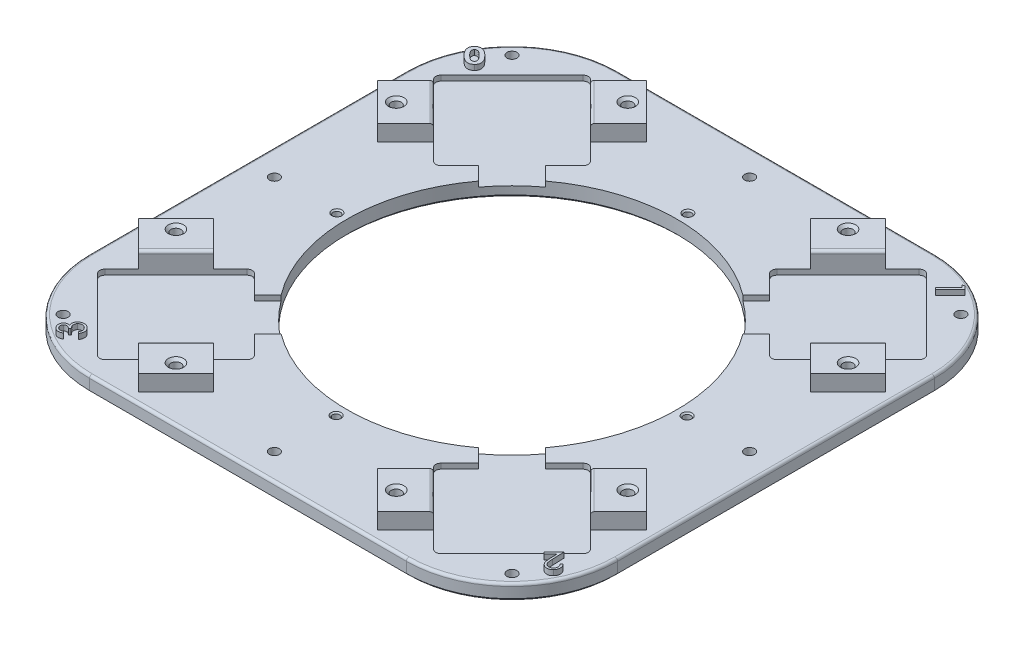
SolidWorks part; units mm, degrees
ref_plane "Спереди" through (0, 0, 0) normal (0, 0, 1) x (1, 0, 0)
ref_plane "Сверху" through (0, 0, 0) normal (0, 1, 0) x (1, 0, 0)
ref_plane "Справа" through (0, 0, 0) normal (1, 0, 0) x (0, 0, -1)
sketch "Эскиз1" plane through (0, 0, 0) normal (0, 1, 0) x (1, 0, 0)
  line L1 (-100, -100) -> (100, -100)
  line L2 (-100, -100) -> (-100, 100)
  line L3 (-100, 100) -> (100, 100)
  line L4 (100, -100) -> (100, 100)
  line L5 (0, 100) -> (0, -100) construction
  line L6 (-100, 0) -> (100, 0) construction
  line L11 (0, 75) -> (0, -75) construction
  line L12 (-39.5, 0) -> (39.5, 0) construction
  line L13 (-85, -85) -> (85, -85) construction
  line L14 (-85, -85) -> (-85, 85) construction
  line L15 (-85, 85) -> (85, 85) construction
  line L16 (85, -85) -> (85, 85) construction
  line L17 (0, 85) -> (0, -85) construction
  line L18 (-85, 0) -> (85, 0) construction
  circle A8 centre (-90, 0) radius 1.9
  circle A9 centre (0, 90) radius 1.9
  circle A10 centre (90, 0) radius 1.9
  circle A11 centre (0, -90) radius 1.9
  circle A12 centre (-85, 85) radius 1.9
  circle A13 centre (85, 85) radius 1.9
  circle A14 centre (85, -85) radius 1.9
  circle A15 centre (-85, -85) radius 1.9
  point P0 (0, 0)
  point P4 (0, 0)
  point P11 (0, 0)
  point P27 (0, 0)
  dimension "D6" = 90
  dimension "D2" = 3.8
  dimension "D1" = 200
  dimension "D8" = 170
  dimension "D7" = 4
extrude "Бобышка-Вытянуть1" add sketch "Эскиз1" along normal blind 6
sketch "Эскиз2" plane through (0, 6, 0) normal (0, 1, 0) x (1, 0, 0)
  line L0 (0, 72.2532) -> (0, 0) construction
  line L1 (0, 0) -> (100, 100) construction
  line L2 (63.6396, 33.9411) -> (33.9411, 63.6396)
  line L3 (63.6396, 33.9411) -> (93.3381, 63.6396)
  line L4 (33.9411, 63.6396) -> (63.6396, 93.3381)
  line L5 (93.3381, 63.6396) -> (63.6396, 93.3381)
  line L6 (63.6396, 33.9411) -> (63.6396, 93.3381) construction
  line L7 (33.9411, 63.6396) -> (93.3381, 63.6396) construction
  line L8 (33.9411, -63.6396) -> (63.6396, -33.9411)
  line L9 (33.9411, -63.6396) -> (63.6396, -93.3381)
  line L10 (63.6396, -93.3381) -> (93.3381, -63.6396)
  line L11 (63.6396, -33.9411) -> (93.3381, -63.6396)
  line L12 (-63.6396, -33.9411) -> (-33.9411, -63.6396)
  line L13 (-63.6396, -33.9411) -> (-93.3381, -63.6396)
  line L14 (-93.3381, -63.6396) -> (-63.6396, -93.3381)
  line L15 (-33.9411, -63.6396) -> (-63.6396, -93.3381)
  line L16 (-33.9411, 63.6396) -> (-63.6396, 33.9411)
  line L17 (-33.9411, 63.6396) -> (-63.6396, 93.3381)
  line L18 (-63.6396, 93.3381) -> (-93.3381, 63.6396)
  line L19 (-63.6396, 33.9411) -> (-93.3381, 63.6396)
  line L20 (0, 0) -> (119.0497, 0) construction
  point P6 (63.6396, 63.6396)
  point P24 (0, 0)
  dimension "D1" = 42
  dimension "D2" = 90
  dimension "D4" = 63.6396
  dimension "D5" = 63.6396
  dimension "D3" = 4
extrude "Вырез-Вытянуть1" cut sketch "Эскиз2" against normal blind 2
fillet "Скругление1" radius 2 16 edges at (63.6396, 5, -33.9411) (33.9411, 5, -63.6396) (93.3381, 5, -63.6396) (63.6396, 5, -93.3381) (-63.6396, 5, -93.3381) (-63.6396, 5, -33.9411) (-93.3381, 5, -63.6396) (-33.9411, 5, -63.6396) (63.6396, 5, 93.3381) (93.3381, 5, 63.6396) (63.6396, 5, 33.9411) (33.9411, 5, 63.6396) (-63.6396, 5, 93.3381) (-33.9411, 5, 63.6396) (-63.6396, 5, 33.9411) (-93.3381, 5, 63.6396)
sketch "Эскиз3" plane through (0, 6, 0) normal (0, 1, 0) x (1, 0, 0)
  line L0 (48.7904, 48.7904) -> (67.3817, 67.3817) construction
  line L1 (35.3553, 62.2254) -> (62.2254, 35.3553) construction
  line L2 (48.7904, 78.4889) -> (78.4889, 48.7904) construction
  line L3 (62.2254, 91.9239) -> (35.3553, 65.0538) construction
  line L4 (65.0538, 35.3553) -> (91.9239, 62.2254) construction
  line L5 (41.7193, 71.4178) -> (55.8614, 85.5599)
  line L6 (41.7193, 71.4178) -> (31.1127, 82.0244)
  line L7 (55.8614, 85.5599) -> (45.2548, 96.1665)
  line L8 (31.1127, 82.0244) -> (45.2548, 96.1665)
  line L9 (62.2254, 91.9239) -> (35.3553, 65.0538) construction
  line L10 (85.5599, 55.8614) -> (96.1665, 45.2548)
  line L11 (82.0244, 31.1127) -> (96.1665, 45.2548)
  line L12 (71.4178, 41.7193) -> (82.0244, 31.1127)
  line L13 (71.4178, 41.7193) -> (85.5599, 55.8614)
  line L44 (65.0538, 35.3553) -> (91.9239, 62.2254) construction
  line L45 (0, 128.3294) -> (0, 0) construction
  line L64 (0, 0) -> (145.1139, 0) construction
  line L65 (62.2254, 91.9239) -> (35.3553, 65.0538) construction
  line L90 (48.7904, -78.4889) -> (78.4889, -48.7904) construction
  line L91 (48.7904, -48.7904) -> (67.3817, -67.3817) construction
  line L92 (71.4178, -41.7193) -> (85.5599, -55.8614)
  line L93 (71.4178, -41.7193) -> (82.0244, -31.1127)
  line L94 (82.0244, -31.1127) -> (96.1665, -45.2548)
  line L95 (85.5599, -55.8614) -> (96.1665, -45.2548)
  line L96 (31.1127, -82.0244) -> (45.2548, -96.1665)
  line L97 (55.8614, -85.5599) -> (45.2548, -96.1665)
  line L98 (41.7193, -71.4178) -> (31.1127, -82.0244)
  line L99 (41.7193, -71.4178) -> (55.8614, -85.5599)
  line L100 (-48.7904, -48.7904) -> (-67.3817, -67.3817) construction
  line L101 (-48.7904, -78.4889) -> (-78.4889, -48.7904) construction
  line L102 (-48.7904, 78.4889) -> (-78.4889, 48.7904) construction
  line L103 (-48.7904, 48.7904) -> (-67.3817, 67.3817) construction
  line L104 (-41.7193, -71.4178) -> (-55.8614, -85.5599)
  line L105 (-41.7193, -71.4178) -> (-31.1127, -82.0244)
  line L106 (-55.8614, -85.5599) -> (-45.2548, -96.1665)
  line L107 (-31.1127, -82.0244) -> (-45.2548, -96.1665)
  line L108 (-85.5599, -55.8614) -> (-96.1665, -45.2548)
  line L109 (-82.0244, -31.1127) -> (-96.1665, -45.2548)
  line L110 (-71.4178, -41.7193) -> (-82.0244, -31.1127)
  line L111 (-71.4178, -41.7193) -> (-85.5599, -55.8614)
  line L112 (-71.4178, 41.7193) -> (-85.5599, 55.8614)
  line L113 (-71.4178, 41.7193) -> (-82.0244, 31.1127)
  line L114 (-82.0244, 31.1127) -> (-96.1665, 45.2548)
  line L115 (-85.5599, 55.8614) -> (-96.1665, 45.2548)
  line L116 (-31.1127, 82.0244) -> (-45.2548, 96.1665)
  line L117 (-55.8614, 85.5599) -> (-45.2548, 96.1665)
  line L118 (-41.7193, 71.4178) -> (-31.1127, 82.0244)
  line L119 (-41.7193, 71.4178) -> (-55.8614, 85.5599)
  point P16 (48.7904, 78.4889)
  dimension "D1" = 20
  dimension "D2" = 15
extrude "Бобышка-Вытянуть3" add sketch "Эскиз3" along normal blind 6
fillet "Скругление4" radius 40 4 edges at (100, 3, -100) (100, 3, 100) (-100, 3, 100) (-100, 3, -100)
sketch "Эскиз4" plane through (0, 12, 0) normal (0, 1, 0) x (1, 0, 0)
  line L0 (89.0955, 38.1838) -> (38.1838, 89.0955) construction
  line L1 (82.0244, 31.1127) -> (96.1665, 45.2548) construction
  line L2 (45.2548, 96.1665) -> (31.1127, 82.0244) construction
  line L3 (41.7193, 71.4178) -> (55.8614, 85.5599) construction
  line L4 (48.7904, 48.7904) -> (78.4889, 78.4889) construction
  line L5 (35.3553, 62.2254) -> (62.2254, 35.3553) construction
  line L6 (91.9239, 65.0538) -> (65.0538, 91.9239) construction
  line L7 (0, 119.2498) -> (0, 0) construction
  line L8 (0, 0) -> (156.895, 0) construction
  line L9 (48.7904, -48.7904) -> (78.4889, -78.4889) construction
  line L10 (89.0955, -38.1838) -> (38.1838, -89.0955) construction
  line L11 (-89.0955, -38.1838) -> (-38.1838, -89.0955) construction
  line L12 (-48.7904, -48.7904) -> (-78.4889, -78.4889) construction
  line L13 (-48.7904, 48.7904) -> (-78.4889, 78.4889) construction
  line L14 (-89.0955, 38.1838) -> (-38.1838, 89.0955) construction
  circle A0 centre (41.7193, 85.5599) radius 1.9
  circle A1 centre (85.5599, 41.7193) radius 1.9
  circle A14 centre (85.5599, -41.7193) radius 1.9
  circle A15 centre (41.7193, -85.5599) radius 1.9
  circle A16 centre (-41.7193, -85.5599) radius 1.9
  circle A17 centre (-85.5599, -41.7193) radius 1.9
  circle A18 centre (-85.5599, 41.7193) radius 1.9
  circle A19 centre (-41.7193, 85.5599) radius 1.9
  dimension "D1" = 10
  dimension "D3" = 62
  dimension "D2" = 3.8
  dimension "D4" = 31
extrude "Вырез-Вытянуть2" cut sketch "Эскиз4" against normal blind 8
sketch "Эскиз7" plane through (0, 6, 0) normal (0, 1, 0) x (1, 0, 0)
  line L0 (0, 76.3028) -> (0, 0) construction
  line L1 (0, 0) -> (74.3797, 74.3797) construction
  line L2 (20, 6) -> (60, 6)
  line L3 (-6, 20) -> (6, 20)
  line L4 (-6, 20) -> (-6, 60)
  line L5 (-6, 60) -> (6, 60)
  line L6 (6, 20) -> (6, 60)
  line L7 (0, 60) -> (0, 20) construction
  line L8 (-6, 40) -> (6, 40) construction
  line L9 (20, 6) -> (20, -6)
  line L10 (20, -6) -> (60, -6)
  line L11 (60, 6) -> (60, -6)
  line L12 (6, -20) -> (6, -60)
  line L13 (6, -20) -> (-6, -20)
  line L14 (-6, -20) -> (-6, -60)
  line L15 (6, -60) -> (-6, -60)
  line L16 (-20, -6) -> (-60, -6)
  line L17 (-20, -6) -> (-20, 6)
  line L18 (-20, 6) -> (-60, 6)
  line L19 (-60, -6) -> (-60, 6)
  circle A0 centre (28.2843, 28.2843) radius 12
  circle A1 centre (28.2843, -28.2843) radius 12
  circle A2 centre (-28.2843, -28.2843) radius 12
  circle A3 centre (-28.2843, 28.2843) radius 12
  point P6 (0, 40)
  point P15 (0, 0)
  point P32 (0, 0)
  dimension "D1" = 40
  dimension "D2" = 24
  dimension "D4" = 12
  dimension "D5" = 40
  dimension "D6" = 40
  dimension "D3" = 4
  dimension "D7" = 4
extrude "Вырез-Вытянуть3" cut sketch "Эскиз7" against normal blind 6
sketch "Эскиз8" plane through (0, 6, 0) normal (0, 1, 0) x (1, 0, 0)
  line L0 (48.7904, 48.7904) -> (72.3205, 72.3205) construction
  line L1 (35.3553, 62.2254) -> (62.2254, 35.3553) construction
  line L2 (44.5477, 31.8198) -> (31.8198, 44.5477)
  line L3 (44.5477, 31.8198) -> (65.7609, 53.033)
  line L4 (31.8198, 44.5477) -> (53.033, 65.7609)
  line L5 (65.7609, 53.033) -> (53.033, 65.7609)
  line L6 (44.5477, 31.8198) -> (53.033, 65.7609) construction
  line L7 (31.8198, 44.5477) -> (65.7609, 53.033) construction
  line L20 (0, 107.5006) -> (0, 0) construction
  line L21 (0, 0) -> (140.6034, 0) construction
  line L22 (31.8198, -44.5477) -> (65.7609, -53.033) construction
  line L23 (44.5477, -31.8198) -> (53.033, -65.7609) construction
  line L24 (48.7904, -48.7904) -> (72.3205, -72.3205) construction
  line L25 (65.7609, -53.033) -> (53.033, -65.7609)
  line L26 (31.8198, -44.5477) -> (53.033, -65.7609)
  line L27 (44.5477, -31.8198) -> (65.7609, -53.033)
  line L28 (44.5477, -31.8198) -> (31.8198, -44.5477)
  line L29 (-48.7904, -48.7904) -> (-72.3205, -72.3205) construction
  line L30 (-44.5477, -31.8198) -> (-53.033, -65.7609) construction
  line L31 (-31.8198, -44.5477) -> (-65.7609, -53.033) construction
  line L32 (-31.8198, 44.5477) -> (-65.7609, 53.033) construction
  line L33 (-44.5477, 31.8198) -> (-53.033, 65.7609) construction
  line L34 (-48.7904, 48.7904) -> (-72.3205, 72.3205) construction
  line L35 (-44.5477, -31.8198) -> (-31.8198, -44.5477)
  line L36 (-44.5477, -31.8198) -> (-65.7609, -53.033)
  line L37 (-31.8198, -44.5477) -> (-53.033, -65.7609)
  line L38 (-65.7609, -53.033) -> (-53.033, -65.7609)
  line L39 (-65.7609, 53.033) -> (-53.033, 65.7609)
  line L40 (-31.8198, 44.5477) -> (-53.033, 65.7609)
  line L41 (-44.5477, 31.8198) -> (-65.7609, 53.033)
  line L42 (-44.5477, 31.8198) -> (-31.8198, 44.5477)
  point P24 (0, 16.9706)
  dimension "D1" = 18
  dimension "D2" = 30
extrude "Вырез-Вытянуть4" cut sketch "Эскиз8" against normal blind 2
fillet "Скругление6" radius 1 8 edges at (78.4889, 12, -48.7904) (48.7904, 12, -78.4889) (-78.4889, 12, 48.7904) (-48.7904, 12, 78.4889) (48.7904, 12, 78.4889) (78.4889, 12, 48.7904) (-78.4889, 12, -48.7904) (-48.7904, 12, -78.4889)
sketch "Эскиз9" plane through (0, 6, 0) normal (0, 1, 0) x (1, 0, 0)
  line L0 (-70.7105, 0.151) -> (0.151, 70.7105) construction
  line L1 (-70.7105, 0.151) -> (-0.151, -70.7105) construction
  line L2 (0.151, 70.7105) -> (70.7105, -0.151) construction
  line L3 (-0.151, -70.7105) -> (70.7105, -0.151) construction
  line L4 (-70.7105, 0.151) -> (70.7105, -0.151) construction
  line L5 (0.151, 70.7105) -> (-0.151, -70.7105) construction
  line L6 (0, 0) -> (60.8554, 60.8554) construction
  circle A0 centre (0.1419, 66.4679) radius 1.4
  circle A4 centre (-0.1419, -66.4679) radius 1.4
  circle A5 centre (66.4679, -0.1419) radius 1.4
  circle A6 centre (-66.4679, 0.1419) radius 1.4
  point P1 (0, 0)
  dimension "D2" = 2.8
  dimension "D3" = 3
  dimension "D4" = 3
  dimension "D5" = 94
  dimension "D1" = 100
extrude "Вырез-Вытянуть5" cut sketch "Эскиз9" against normal blind 10
sketch "Эскиз10" plane through (0, 6, 0) normal (0, 1, 0) x (1, 0, 0)
  line L0 (-89.4334, 70.8427) -> (-83.9454, 76.3307) construction
  line L1 (0, 108.5259) -> (0, 0) construction
  line L2 (71.3984, 88.9173) -> (76.8147, 83.501) construction
  line L3 (90.0364, -69.9365) -> (84.274, -75.6989) construction
  line L4 (-72.0522, -89.0668) -> (-79.6906, -81.6618) construction
  text T0 "<b>0</b>\r\n" font "Century Gothic" height 8
  text T1 "1\r\n" font "Century Gothic" height 8
  text T2 "2" font "Century Gothic" height 8
  text T3 "3\r\n" font "Century Gothic" height 8
extrude "Бобышка-Вытянуть6" add sketch "Эскиз10" along normal blind 2
fillet "Скругление9" radius 1 8 edges at (88.2843, 6, 88.2843) (0, 6, 100) (-88.2843, 6, 88.2843) (-100, 6, 0) (-88.2843, 6, -88.2843) (0, 6, -100) (88.2843, 6, -88.2843) (100, 6, 0)
sketch "Эскиз11" plane through (0, 6, 0) normal (0, 1, 0) x (1, 0, 0)
  circle A0 centre (0, 0) radius 62.5
  dimension "D1" = 125
extrude "Вырез-Вытянуть6" cut sketch "Эскиз11" against normal through all both and the other way through all
chamfer "Фаска1" distance 1 angle 45 21 edges at (100, 0, 0) (88.2843, 0, -88.2843) (88.2843, 0, 88.2843) (0, 0, -100) (0, 0, 100) (-88.2843, 0, -88.2843) (-88.2843, 0, 88.2843) (-100, 0, 0) (-85, 0, 86.9) (85, 0, -83.1) (-90, 0, 1.9) (90, 0, 1.9) (0, 0, -88.1) (0, 0, 91.9) (-85, 0, -83.1) (85, 0, 86.9) (-66.4679, 0, -1.5419) (66.4679, 0, -1.2581) (-0.1419, 0, 65.0679) (0.1419, 0, -67.8679) (0, 0, 62.5)
chamfer "Фаска2" distance 1 angle 45 8 edges at (-85.5599, 12, 39.8193) (-41.7193, 12, 87.4599) (41.7193, 12, 83.6599) (85.5599, 12, 43.6193) (85.5599, 12, -43.6193) (41.7193, 12, -83.6599) (-85.5599, 12, -39.8193) (-41.7193, 12, -87.4599)
chamfer "Фаска3" distance 0.5 angle 45 4 edges at (-66.4679, 6, -1.5419) (-0.1419, 6, 65.0679) (66.4679, 6, 1.5419) (0.1419, 6, -65.0679)
